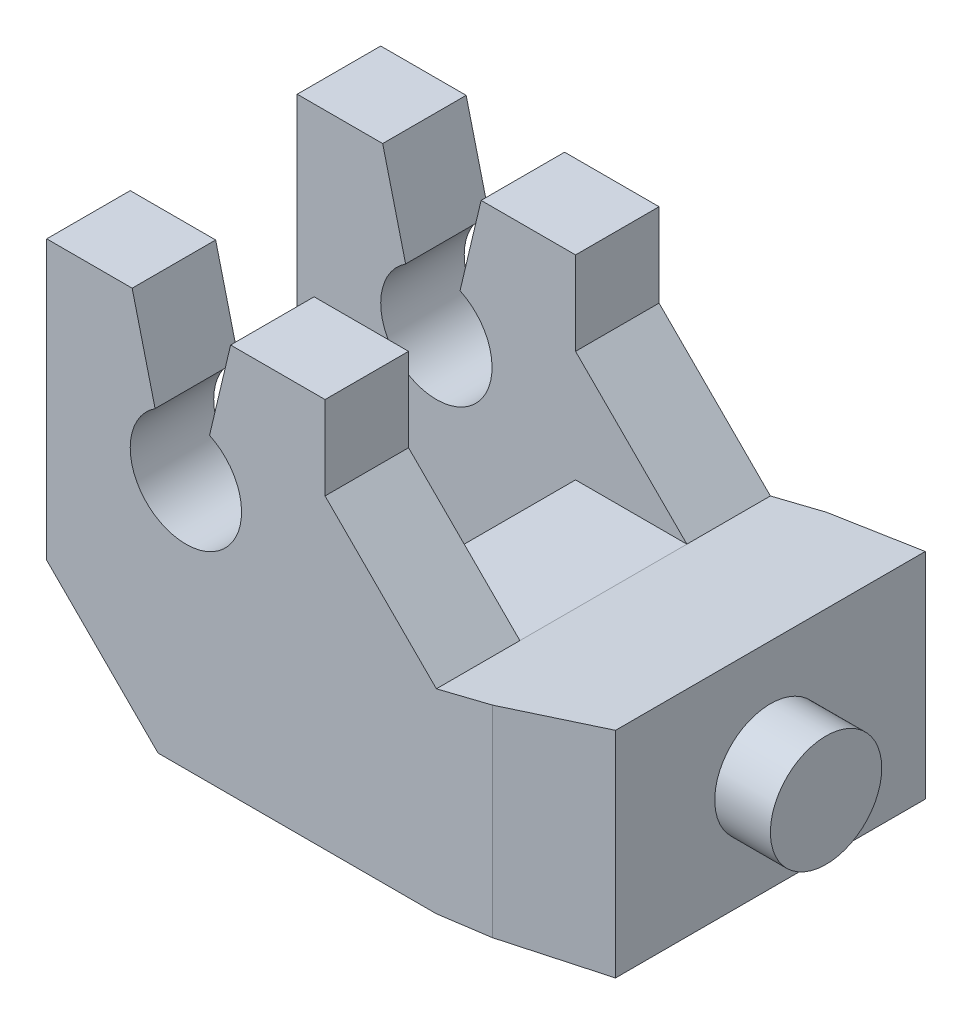
SolidWorks part; units mm, degrees
ref_plane "Front Plane" through (0, 0, 0) normal (0, 0, 1) x (1, 0, 0)
ref_plane "Top Plane" through (0, 0, 0) normal (0, 1, 0) x (1, 0, 0)
ref_plane "Right Plane" through (0, 0, 0) normal (1, 0, 0) x (0, 0, -1)
sketch "Sketch1" plane through (0, 0, 0) normal (0, 0, 1) x (1, 0, 0)
  line L0 (-25, 25) -> (25, 25)
  line L1 (25, 25) -> (25, -10)
  line L2 (25, -10) -> (45, -10)
  line L3 (45, -10) -> (130, 11.1135)
  line L4 (130, 11.1135) -> (165, 11.1135)
  line L5 (165, 11.1135) -> (165, -33.8865)
  line L6 (165, -33.8865) -> (130, -33.8865)
  line L7 (130, -33.8865) -> (45.0023, -45.0023)
  line L8 (45.0023, -45.0023) -> (-4.9977, -45.0023)
  line L9 (-4.9977, -45.0023) -> (-25, -25)
  line L10 (-25, -25) -> (-25, 25)
  line L11 (75, -2.5482) -> (75, -41.0792)
  line L12 (25, -10) -> (-4.9977, -45.0023)
  circle A1 centre (0, 0) radius 10
  point P16 (0, 25)
  point P19 (-25, 0)
  dimension "D1" = 20
  dimension "D2" = 50
  dimension "D3" = 50
  dimension "D4" = 35
  dimension "D5" = 20
  dimension "D6" = 135
  dimension "D7" = 50
  dimension "D8" = 190
  dimension "D9" = 100
  dimension "D10" = 87.583
  dimension "D11" = 35
  dimension "D12" = 45
extrude "Boss-Extrude2" add sketch "Sketch1" along normal mid plane 60 contours L12 L1 L0 L10 L9 A1 | L2 L12 L8 L7 L11 L3 | L3 L11 L7 L6 L5 L4 region at (0, 24.1397, 0) region at (42.4484, -27.4478, 0) region at (121.2251, -14.3996, 0)
sketch "Sketch3" plane through (0, 0, 0) normal (0, 0, 1) x (1, 0, 0)
sketch "Sketch4" plane through (0, 0, 0) normal (0, 0, 1) x (1, 0, 0)
  line L0 (75, -2.5482) -> (75, -41.0792) construction
  line L1 (25, -10) -> (45, -10) construction
  line L2 (45, -10) -> (130, 11.1135) construction
  line L3 (130, 11.1135) -> (165, 11.1135) construction
  line L4 (165, 11.1135) -> (165, -33.8865) construction
  line L5 (165, -33.8865) -> (130, -33.8865) construction
  line L6 (130, -33.8865) -> (45.0023, -45.0023) construction
  line L7 (45.0023, -45.0023) -> (-4.9977, -45.0023) construction
  line L8 (25, 25) -> (25, -10) construction
  line L9 (-25, 25) -> (25, 25) construction
  line L10 (-25, -25) -> (-25, 25) construction
  line L11 (-4.9977, -45.0023) -> (-25, -25) construction
  line L12 (25, -10) -> (-4.9977, -45.0023) construction
  line L13 (75, -2.5482) -> (75, -41.0792)
  line L14 (25, -10) -> (45, -10)
  line L15 (45, -10) -> (130, 11.1135)
  line L16 (130, 11.1135) -> (165, 11.1135)
  line L17 (165, 11.1135) -> (165, -33.8865)
  line L18 (165, -33.8865) -> (130, -33.8865)
  line L19 (130, -33.8865) -> (45.0023, -45.0023)
  line L20 (45.0023, -45.0023) -> (-4.9977, -45.0023)
  line L21 (25, 25) -> (25, -10)
  line L22 (-25, 25) -> (25, 25)
  line L23 (-25, -25) -> (-25, 25)
  line L24 (-4.9977, -45.0023) -> (-25, -25)
  line L25 (25, -10) -> (-4.9977, -45.0023)
  circle A1 centre (0, 0) radius 10
  circle A2 centre (0, 0) radius 10
  dimension "D1" = 0
extrude "Cut-Extrude1" cut sketch "Sketch4" against normal mid plane 30 contours L25 L21 L22 L23 L24 A2 region at (9.3479, -26.9413, 0)
chamfer "Chamfer1" distance 20 angle 45 2 edges at (25, -10, -22.5) (25, -10, 22.5)
sketch "Sketch5" plane through (0, 0, 0) normal (0, 1, 0) x (1, 0, 0)
  line L2 (165, 30) -> (165, -30)
  line L3 (165, -30) -> (55.0742, -30)
  line L4 (45, -30) -> (130, -30) construction
  line L5 (55.0742, -30) -> (165, -18)
  line L6 (165, 30) -> (55.0742, 30)
  line L7 (55.0742, 30) -> (165, 18)
  dimension "D2" = 6.23
extrude "Cut-Extrude2" cut sketch "Sketch5" against normal through all both and the other way through all contours L5 L3 L2 | L6 L7 L2 region at (128.3581, 0, 26) region at (128.3581, 0, -26)
sketch "Sketch6" plane through (165, 0, 0) normal (1, 0, 0) x (0, 0, -1)
  line L0 (-18, -33.8865) -> (18, -33.8865)
  line L1 (18, -33.8865) -> (18, -17.8865)
  line L2 (18, -33.8865) -> (18, 11.1135) construction
  line L3 (-18, -33.8865) -> (-18, -17.8865)
  line L4 (-18, -33.8865) -> (-18, 11.1135) construction
  line L6 (-18, 11.1135) -> (18, 11.1135) construction
  arc A1 (-18, -17.8865) -> (18, -17.8865) centre (0, 0) ccw
  circle A2 centre (0, -1.8865) radius 9
  dimension "D1" = 16
  dimension "D2" = 18
  dimension "D3" = 13
extrude "Boss-Extrude3" add sketch "Sketch6" along normal blind 45 contours A1 L1 L0 L3
sketch "Sketch7" plane through (165, 0, 0) normal (1, 0, 0) x (0, 0, -1)
extrude "Cut-Extrude3" cut sketch "Sketch6<3>" against normal blind 15 and the other way through all contours A2 region at (165, -1.8865, 0)
sketch "Sketch6<3>" plane through (165, 0, 0) normal (1, 0, 0) x (0, 0, -1) same geometry as "Sketch6"
sketch "Sketch8" plane through (0, -33.8865, 0) normal (0, -1, 0) x (1, 0, 0)
  line L0 (210, 18) -> (165, 18) construction
  line L1 (195, 18) -> (210, 18)
  line L2 (195, 18) -> (195, -18)
  line L3 (195, -18) -> (210, -18)
  line L4 (210, 18) -> (210, -18)
  dimension "D1" = 15
extrude "Boss-Extrude4" add sketch "Sketch8" against normal up to vertex (45 mm away) up to point (165, 11.1136, 18)
sketch "Sketch10" plane through (165, 0, 0) normal (1, 0, 0) x (0, 0, -1)
  line L3 (-18, 11.1135) -> (-18, -17.8865)
  line L4 (18, -17.8865) -> (18, 11.1135)
  line L5 (18, 11.1135) -> (-18, 11.1135)
  line L6 (-18, 11.1135) -> (-18, -17.8865)
  line L7 (18, -17.8865) -> (18, 11.1135)
  line L8 (18, 11.1135) -> (-18, 11.1135)
  circle A0 centre (0, -1.8865) radius 9 construction
  arc A1 (-18, -17.8865) -> (18, -17.8865) centre (0, 0) ccw
  arc A2 (-18, -17.8865) -> (18, -17.8865) centre (0, 0) ccw
  circle A3 centre (0, -1.8865) radius 9
  circle M5 centre (0, -1.8865) radius 9
  dimension "D1" = 0
extrude "Cut-Extrude4" cut sketch "Sketch10" along normal through all contours M5 region at (165, -1.8865, 0)
sketch "Sketch11" plane through (0, -33.8865, 0) normal (0, -1, 0) x (1, 0, 0)
  line L0 (130, 21.8208) -> (130, -21.8208)
  line L1 (130, -21.8208) -> (165, -18)
  line L2 (165, -18) -> (130, -21.8208) construction
  line L3 (210, -18) -> (165, -18) construction
  line L4 (165, -18) -> (210, -18)
  line L5 (210, -18) -> (210, 18)
  line L6 (210, 18) -> (165, 18)
  line L7 (210, 18) -> (165, 18) construction
  line L8 (165, 18) -> (130, 21.8208)
extrude "Boss-Extrude5" add sketch "Sketch11" along normal blind 10
chamfer "Chamfer2" distance 12 angle 45 1 edges at (130, -43.8865, 0)
sketch "Sketch13" plane through (0, 0, 18) normal (0, 0, 1) x (1, 0, 0)
  line L0 (165, -17.8865) -> (195, -17.8865)
  arc A0 (165, -17.8865) -> (195, -17.8865) centre (180, -6.2245) ccw
  dimension "D1" = 38
extrude "Cut-Extrude5" cut sketch "Sketch13" against normal blind 40
sketch "Sketch14" plane through (0, 0, 0) normal (0, 1, 0) x (1, 0, 0)
  line L1 (-25, -30) -> (75, -30)
  line L2 (-25, -30) -> (-25, 30)
  line L3 (-25, 30) -> (75, 30)
  line L4 (75, -30) -> (75, 30)
  dimension "D1" = 100
extrude "Cut-Extrude6" cut sketch "Sketch14" against normal through all both and the other way through all flip side to cut
sketch "Sketch15" plane through (75, 0, 0) normal (1, 0, 0) x (0, 0, -1)
  circle A0 centre (0, -22.3255) radius 10
  dimension "D1" = 20
extrude "Boss-Extrude6" add sketch "Sketch15" along normal blind 10
sketch "Sketch16" plane through (0, 0, -30) normal (0, 0, -1) x (-1, 0, 0)
  line L0 (-8.033, 25) -> (-4.2505, 9.0517)
  line L1 (9.6508, 25) -> (5.5309, 8.3312)
  line L9 (-45, -10) -> (-55.0742, -7.4976)
  line L10 (-55.0742, -7.4976) -> (-55.0742, -43.6851)
  line L11 (-55.0742, -43.6851) -> (-45.0023, -45.0023)
  line L12 (-45.0023, -45.0023) -> (4.9977, -45.0023)
  line L13 (4.9977, -45.0023) -> (25, -25)
  line L14 (25, -25) -> (25, 25)
  line L15 (25, 25) -> (-25, 25)
  line L16 (-25, 25) -> (-25, 10)
  line L17 (-25, 10) -> (-45, -10)
  line L24 (9.6508, 25) -> (-8.033, 25)
  circle A0 centre (0, 0) radius 10 construction
  arc A1 (5.5309, 8.3312) -> (-4.2505, 9.0517) centre (0, 0) ccw
  point P16 (9.6508, 25)
  point P17 (0, 0)
  point P18 (0, 0)
  dimension "D1" = 0
extrude "Cut-Extrude7" cut sketch "Sketch16" against normal up to surface (60 mm away) up to face at (10, 0, 30)
